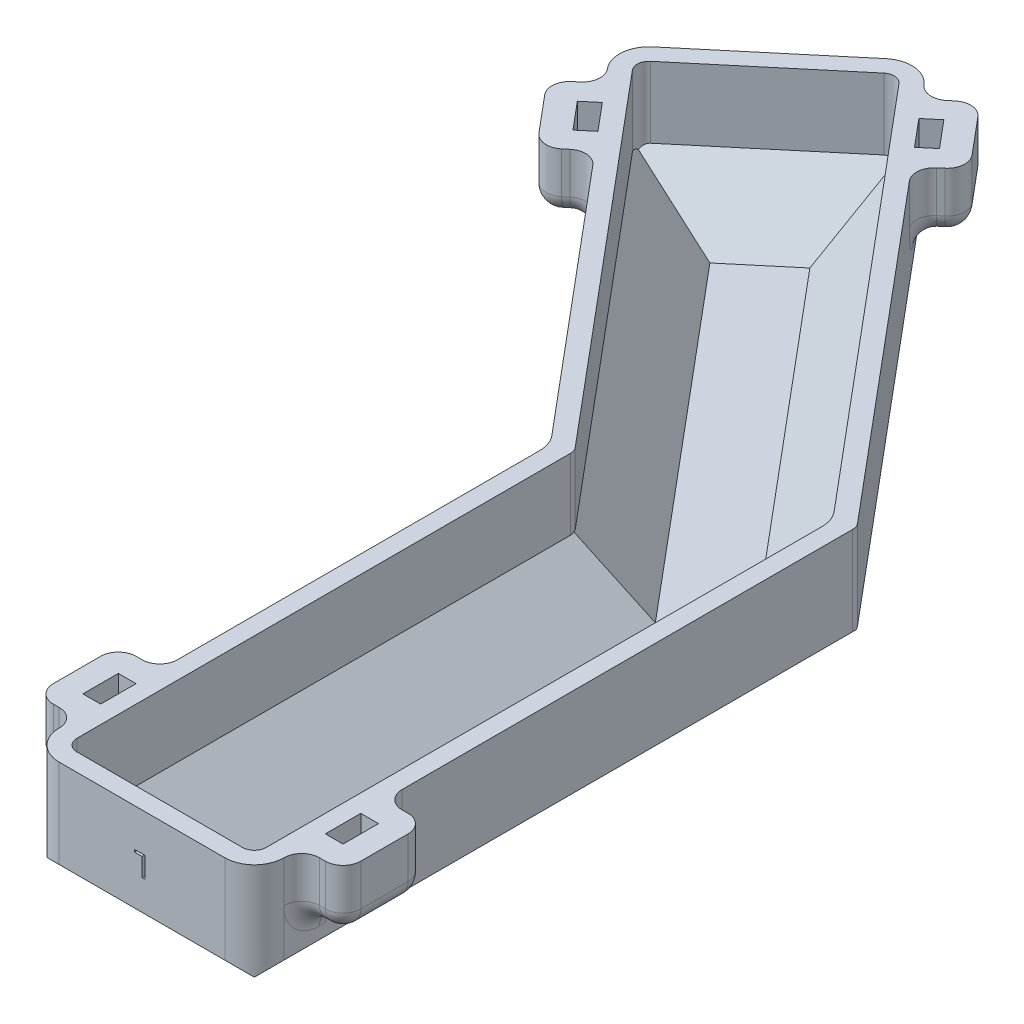
SolidWorks part; units mm, degrees
ref_plane "Front Plane" through (0, 0, 0) normal (0, 0, 1) x (1, 0, 0)
ref_plane "Top Plane" through (0, 0, 0) normal (0, 1, 0) x (1, 0, 0)
ref_plane "Right Plane" through (0, 0, 0) normal (1, 0, 0) x (0, 0, -1)
sketch "Sketch1" plane through (0, 0, 0) normal (0, 1, 0) x (1, 0, 0)
  line L0 (0, -95) -> (0, 0) construction
  line L1 (0, 0) -> (-57.8509, 68.944) construction
  line L2 (19, -95) -> (19, 6.9154)
  line L3 (-19, -95) -> (-19, -6.9154)
  line L4 (-19, -95) -> (19, -95)
  line L5 (19, 6.9154) -> (-43.296, 81.157)
  line L6 (-72.4057, 56.731) -> (-43.296, 81.157)
  line L7 (-72.4057, 56.731) -> (-19, -6.9154)
  line L8 (-68.1792, 56.3613) -> (-43.6658, 76.9305) construction
  line L9 (-68.1792, 56.3613) -> (-16, -5.8235) construction
  line L10 (-16, -5.8235) -> (-16, -92) construction
  line L11 (-16, -92) -> (16, -92) construction
  line L12 (16, -92) -> (16, 5.8235) construction
  line L13 (16, 5.8235) -> (-43.6658, 76.9305) construction
  point P9 (0, -95)
  point P10 (-57.8509, 68.944)
  point P12 (-55.9225, 66.6459)
  point P13 (0, -92)
  dimension "D1" = 95
  dimension "D2" = 90
  dimension "D3" = 38
  dimension "D4" = 38
  dimension "D5" = 140
  dimension "D6" = 32
  dimension "D7" = 32
  dimension "D8" = 3
  dimension "D9" = 3
extrude "Boss-Extrude1" add sketch "Sketch1" along normal blind 25
sketch "Sketch2" plane through (0, 25, 0) normal (0, 1, 0) x (1, 0, 0)
  line L0 (-68.1792, 56.3613) -> (-43.6658, 76.9305)
  line L1 (-68.1792, 56.3613) -> (-16, -5.8235)
  line L2 (-16, -5.8235) -> (-16, -92)
  line L3 (-16, -92) -> (16, -92)
  line L4 (16, -92) -> (16, 5.8235)
  line L5 (16, 5.8235) -> (-43.6658, 76.9305)
  line L6 (0, 0) -> (-57.8509, 68.944) construction
  line L7 (-43.296, 81.157) -> (-72.4057, 56.731) construction
  line L8 (0, 0) -> (0, -95) construction
  line L9 (-19, -95) -> (19, -95) construction
  point P0 (-55.9225, 66.6459)
  point P1 (0, -92)
  dimension "D1" = 32
  dimension "D2" = 32
  dimension "D3" = 3
  dimension "D4" = 3
extrude "Cut-Extrude1" cut sketch "Sketch2" against normal blind 22
chamfer "Chamfer1" distance 10 angle 45 12 edges at (-55.9225, 3, -66.6459) (-13.8329, 3, -41.377) (16, 3, 43.0882) (0, 3, 92) (-16, 3, 48.9118) (-42.0896, 3, -25.2689) (-45.7029, 0, -24.9078) (-57.8509, 0, -68.944) (-12.148, 0, -44.0362) (19, 0, 44.0423) (-19, 0, 50.9577) (0, 0, 95)
fillet "Fillet1" radius 2 6 edges at (-16, 19, 92) (16, 19, 92) (-16, 19, 5.8235) (19, 17.5, -6.9154) (-68.1792, 19, -56.3613) (-43.6658, 19, -76.9305)
fillet "Fillet2" radius 5 6 edges at (-19, 17.5, 95) (19, 17.5, 95) (-19, 17.5, 6.9154) (16, 19, -5.8235) (-43.296, 17.5, -81.157) (-72.4057, 17.5, -56.731)
sketch "Sketch3" plane through (-14.5548, 0, 12.213) normal (-0.766, 0, 0.6428) x (0.6428, 0, 0.766)
  line L0 (-85, 25) -> (-8.7353, 25) construction
  line L1 (-68, 15) -> (-82, 15)
  line L2 (-68, 15) -> (-68, 25)
  line L3 (-68, 25) -> (-82, 25)
  line L4 (-82, 15) -> (-82, 25)
  line L5 (-68, 15) -> (-82, 25) construction
  line L6 (-68, 25) -> (-82, 15) construction
  line L7 (-85, 25) -> (-85, 10) construction
  point P0 (-75, 20)
  dimension "D1" = 10
  dimension "D2" = 14
  dimension "D3" = 3
sketch "Sketch4" plane through (14.5548, 0, -12.213) normal (0.766, 0, -0.6428) x (-0.6428, 0, -0.766)
  line L0 (-6.1875, 25) -> (85, 25) construction
  line L1 (82, 15) -> (68, 15)
  line L2 (82, 15) -> (82, 25)
  line L3 (82, 25) -> (68, 25)
  line L4 (68, 15) -> (68, 25)
  line L5 (82, 15) -> (68, 25) construction
  line L6 (82, 25) -> (68, 15) construction
  line L7 (85, 10) -> (85, 25) construction
  point P0 (75, 20)
  dimension "D1" = 3
  dimension "D2" = 10
  dimension "D3" = 14
sketch "Sketch6" plane through (-19, 0, 0) normal (-1, 0, 0) x (0, 0, 1)
  line L0 (8.7353, 25) -> (90, 25) construction
  line L1 (87, 15) -> (73, 15)
  line L2 (87, 15) -> (87, 25)
  line L3 (87, 25) -> (73, 25)
  line L4 (73, 15) -> (73, 25)
  line L5 (87, 15) -> (73, 25) construction
  line L6 (87, 25) -> (73, 15) construction
  line L7 (90, 10) -> (90, 25) construction
  point P0 (80, 20)
  dimension "D1" = 3
  dimension "D2" = 14
  dimension "D3" = 10
sketch "Sketch7" plane through (19, 0, 0) normal (1, 0, 0) x (0, 0, -1)
  line L0 (-90, 25) -> (6.1875, 25) construction
  line L1 (-73, 15) -> (-87, 15)
  line L2 (-73, 15) -> (-73, 25)
  line L3 (-73, 25) -> (-87, 25)
  line L4 (-87, 15) -> (-87, 25)
  line L5 (-73, 15) -> (-87, 25) construction
  line L6 (-73, 25) -> (-87, 15) construction
  line L7 (-90, 25) -> (-90, 10) construction
  point P0 (-80, 20)
  dimension "D1" = 10
  dimension "D2" = 14
  dimension "D3" = 3
sketch "Sketch9" plane through (0, 0, 95) normal (0, 0, 1) x (1, 0, 0)
  line L0 (0, 10) -> (0, 25) construction
  line L1 (-14, 10) -> (14, 10) construction
  line L2 (-14, 25) -> (14, 25) construction
  line L3 (14, 17.5) -> (-14, 17.5) construction
  line L4 (14, 10) -> (14, 25) construction
  line L5 (-14, 25) -> (-14, 10) construction
  text T0 "<b><r180>L</r></b>"
extrude "Cut-Extrude4" cut sketch "Sketch9" against normal blind 0.5
extrude "Boss-Extrude2" add sketch "Sketch3" along normal blind 7
extrude "Boss-Extrude3" add sketch "Sketch4" along normal blind 7
extrude "Boss-Extrude4" add sketch "Sketch6" along normal blind 7
extrude "Boss-Extrude5" add sketch "Sketch7" along normal blind 7
sketch "Sketch10" plane through (0, 25, 0) normal (0, 1, 0) x (1, 0, 0)
  line L0 (-66.9904, 45.6101) -> (-64.6923, 47.5385)
  line L1 (-66.9904, 45.6101) -> (-63.1337, 41.0139)
  line L2 (-64.6923, 47.5385) -> (-60.8356, 42.9422)
  line L3 (-63.1337, 41.0139) -> (-60.8356, 42.9422)
  line L4 (-35.5826, 71.9644) -> (-33.2845, 73.8928)
  line L5 (-35.5826, 71.9644) -> (-31.7259, 67.3682)
  line L6 (-33.2845, 73.8928) -> (-29.4277, 69.2965)
  line L7 (-31.7259, 67.3682) -> (-29.4277, 69.2965)
  line L8 (-58.2644, 39.8781) -> (-20.1698, -5.5213) construction
  line L9 (-72.6257, 46.1032) -> (-67.2634, 50.6027) construction
  line L10 (-32.7914, 79.5281) -> (-38.1537, 75.0286) construction
  line L11 (18.5321, 7.4731) -> (-29.1547, 64.304) construction
  line L12 (-22, -77) -> (-19, -77)
  line L13 (-22, -77) -> (-22, -83)
  line L14 (-19, -77) -> (-19, -83)
  line L15 (-22, -83) -> (-19, -83)
  line L16 (19, -77) -> (22, -77)
  line L17 (19, -77) -> (19, -83)
  line L18 (22, -77) -> (22, -83)
  line L19 (19, -83) -> (22, -83)
  line L20 (26, -73) -> (19, -73) construction
  line L21 (19, -73) -> (19, 6.1875) construction
  line L22 (-19, -8.7353) -> (-19, -73) construction
  line L23 (-26, -73) -> (-19, -73) construction
  dimension "D1" = 4
  dimension "D2" = 4
  dimension "D3" = 4
  dimension "D4" = 4
  dimension "D5" = 6
  dimension "D6" = 3
extrude "Cut-Extrude5" cut sketch "Sketch10" against normal through all
fillet "Fillet3" radius 3 36 edges at (-58.2644, 20, -39.8781) (-65.9779, 15, -49.0706) (19, 20, 87) (19, 15, 75) (-19, 20, 87) (-19, 20, 73) (-29.1547, 20, -64.304) (-38.1537, 20, -75.0286) (-60.9456, 15, -37.6283) (-59.55, 15, -41.4101) (-63.6267, 20, -35.3785) (-67.2634, 20, -50.6027) (-72.6257, 20, -46.1032) (-68.1262, 15, -40.7409) (-69.9446, 15, -48.3529) (26, 20, 87) (22.5, 15, 87) (19, 15, 85) (26, 15, 80) (19, 20, 73) (22.5, 15, 73) (26, 20, 73) (-26, 20, 87) (-22.5, 15, 87) (-19, 15, 85) (-19, 15, 75) (-26, 15, 80) (-26, 20, 73) (-22.5, 15, 73) (-30.4403, 15, -65.8361) (-26.4736, 15, -66.5537) (-23.7924, 20, -68.8035) (-35.4726, 15, -77.2784) (-28.2919, 15, -74.1658) (-36.8682, 15, -73.4965) (-32.7914, 20, -79.5281)
